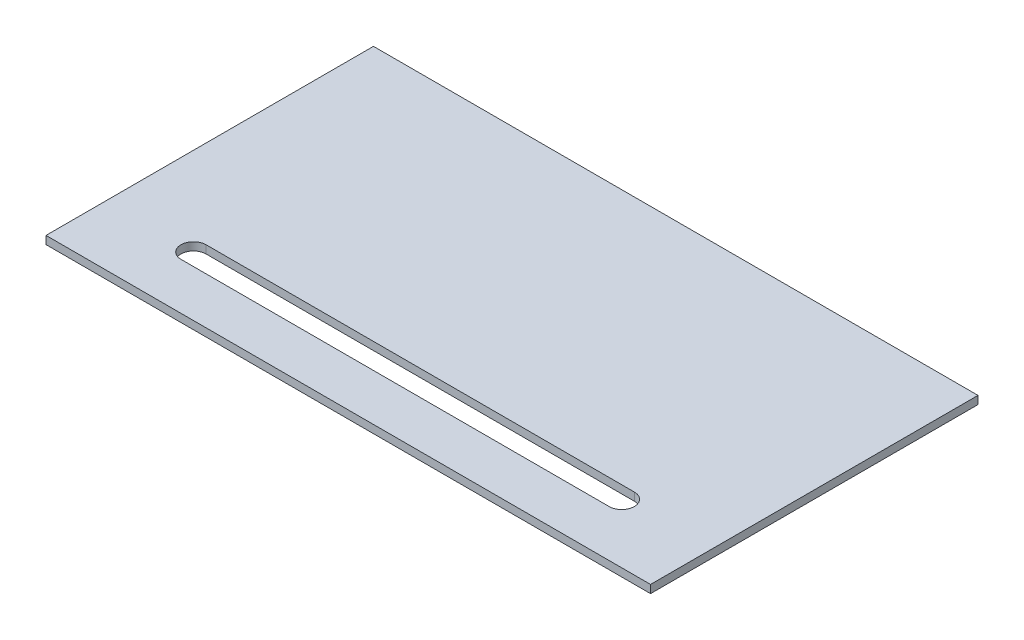
SolidWorks part; units mm, degrees
ref_plane "Front Plane" through (0, 0, 0) normal (0, 0, 1) x (1, 0, 0)
ref_plane "Top Plane" through (0, 0, 0) normal (0, 1, 0) x (1, 0, 0)
ref_plane "Right Plane" through (0, 0, 0) normal (1, 0, 0) x (0, 0, -1)
sketch "Sketch1" plane through (0, 0, 0) normal (0, 1, 0) x (1, 0, 0)
  line L0 (0, 65) -> (0, -65) construction
  line L1 (-120, 65) -> (120, 65)
  line L2 (-120, 65) -> (-120, -65)
  line L3 (-120, -65) -> (120, -65)
  line L4 (120, 65) -> (120, -65)
  line L5 (-111.5875, 55) -> (-111.5875, 45) construction
  line L6 (-113.175, 55) -> (-110, 55) construction
  line L7 (-113.175, 55) -> (-113.175, 45) construction
  line L8 (-113.175, 45) -> (-110, 45) construction
  line L9 (-110, 55) -> (-110, 45) construction
  line L10 (-110, 58.175) -> (-100, 58.175) construction
  line L11 (-110, 58.175) -> (-110, 55) construction
  line L12 (-110, 55) -> (-100, 55) construction
  line L13 (-100, 58.175) -> (-100, 55) construction
  line L14 (-110, 56.5875) -> (-100, 56.5875) construction
  line L15 (100, 56.5875) -> (110, 56.5875) construction
  line L16 (-113.175, 52) -> (-110, 52)
  line L17 (-113.175, 52) -> (-113.175, 48)
  line L18 (-113.175, 48) -> (-110, 48)
  line L19 (-110, 52) -> (-110, 48)
  line L20 (-113.175, 52) -> (-110, 48) construction
  line L21 (-113.175, 48) -> (-110, 52) construction
  line L22 (-107, 55) -> (-103, 55)
  line L23 (-107, 55) -> (-107, 58.175)
  line L24 (-107, 58.175) -> (-103, 58.175)
  line L25 (-103, 55) -> (-103, 58.175)
  line L26 (-107, 55) -> (-103, 58.175) construction
  line L27 (-107, 58.175) -> (-103, 55) construction
  line L28 (110, 55) -> (113.175, 55) construction
  line L29 (110, 55) -> (110, 45) construction
  line L30 (110, 45) -> (113.175, 45) construction
  line L31 (113.175, 55) -> (113.175, 45) construction
  line L32 (100, 58.175) -> (110, 58.175) construction
  line L33 (100, 58.175) -> (100, 55) construction
  line L34 (100, 55) -> (110, 55) construction
  line L35 (110, 58.175) -> (110, 55) construction
  line L36 (111.5875, 55) -> (111.5875, 45) construction
  line L37 (-111.5875, -45) -> (-111.5875, -55) construction
  line L38 (103, 55) -> (107, 55)
  line L39 (103, 55) -> (103, 58.175)
  line L40 (103, 58.175) -> (107, 58.175)
  line L41 (107, 55) -> (107, 58.175)
  line L42 (103, 55) -> (107, 58.175) construction
  line L43 (103, 58.175) -> (107, 55) construction
  line L44 (110, 52) -> (113.175, 52)
  line L45 (110, 52) -> (110, 48)
  line L46 (110, 48) -> (113.175, 48)
  line L47 (113.175, 52) -> (113.175, 48)
  line L48 (110, 52) -> (113.175, 48) construction
  line L49 (110, 48) -> (113.175, 52) construction
  line L50 (-113.175, -45) -> (-110, -45) construction
  line L51 (-113.175, -45) -> (-113.175, -55) construction
  line L52 (-113.175, -55) -> (-110, -55) construction
  line L53 (-110, -45) -> (-110, -55) construction
  line L54 (111.5875, -45) -> (111.5875, -55) construction
  line L55 (-113.175, -52) -> (-110, -52)
  line L56 (-113.175, -52) -> (-113.175, -48)
  line L57 (-113.175, -48) -> (-110, -48)
  line L58 (-110, -52) -> (-110, -48)
  line L59 (-113.175, -52) -> (-110, -48) construction
  line L60 (-113.175, -48) -> (-110, -52) construction
  line L61 (113.175, -55) -> (110, -55) construction
  line L62 (113.175, -55) -> (113.175, -45) construction
  line L63 (113.175, -45) -> (110, -45) construction
  line L64 (110, -55) -> (110, -45) construction
  line L65 (-70, -58.175) -> (-50, -58.175)
  line L66 (110, -52) -> (113.175, -52)
  line L67 (110, -52) -> (110, -48)
  line L68 (110, -48) -> (113.175, -48)
  line L69 (113.175, -52) -> (113.175, -48)
  line L70 (110, -52) -> (113.175, -48) construction
  line L71 (110, -48) -> (113.175, -52) construction
  line L72 (-110, -55) -> (-90, -55)
  line L73 (-110, -55) -> (-110, -58.175)
  line L74 (-110, -58.175) -> (-90, -58.175)
  line L75 (-90, -55) -> (-90, -58.175)
  line L76 (-70, -55) -> (-70, -58.175)
  line L77 (-70, -55) -> (-50, -55)
  line L78 (-50, -55) -> (-50, -58.175)
  line L79 (-30, -58.175) -> (-10, -58.175)
  line L80 (-30, -55) -> (-30, -58.175)
  line L81 (-30, -55) -> (-10, -55)
  line L82 (-10, -55) -> (-10, -58.175)
  line L83 (10, -58.175) -> (30, -58.175)
  line L84 (10, -55) -> (10, -58.175)
  line L85 (10, -55) -> (30, -55)
  line L86 (30, -55) -> (30, -58.175)
  line L87 (50, -58.175) -> (70, -58.175)
  line L88 (50, -55) -> (50, -58.175)
  line L89 (50, -55) -> (70, -55)
  line L90 (70, -55) -> (70, -58.175)
  line L91 (90, -58.175) -> (110, -58.175)
  line L92 (90, -55) -> (90, -58.175)
  line L93 (90, -55) -> (110, -55)
  line L94 (110, -55) -> (110, -58.175)
  line L191 (-68.5, -21.825) -> (-64.5, -21.825)
  line L192 (-68.5, -21.825) -> (-68.5, -25)
  line L193 (-68.5, -25) -> (-64.5, -25)
  line L194 (-64.5, -21.825) -> (-64.5, -25)
  line L195 (-57, -21.825) -> (-53, -21.825)
  line L196 (-57, -21.825) -> (-57, -25)
  line L197 (-57, -25) -> (-53, -25)
  line L198 (-53, -21.825) -> (-53, -25)
  line L199 (-45.5, -21.825) -> (-41.5, -21.825)
  line L200 (-45.5, -21.825) -> (-45.5, -25)
  line L201 (-45.5, -25) -> (-41.5, -25)
  line L202 (-41.5, -21.825) -> (-41.5, -25)
  line L216 (41.5, -25) -> (45.5, -25)
  line L217 (41.5, -25) -> (41.5, -21.825)
  line L218 (41.5, -21.825) -> (45.5, -21.825)
  line L219 (45.5, -25) -> (45.5, -21.825)
  line L220 (53, -25) -> (57, -25)
  line L221 (53, -25) -> (53, -21.825)
  line L222 (53, -21.825) -> (57, -21.825)
  line L223 (57, -25) -> (57, -21.825)
  line L224 (64.5, -25) -> (68.5, -25)
  line L225 (64.5, -25) -> (64.5, -21.825)
  line L226 (64.5, -21.825) -> (68.5, -21.825)
  line L227 (68.5, -25) -> (68.5, -21.825)
  line L240 (-13.5, -21.825) -> (-9.5, -21.825)
  line L241 (-13.5, -21.825) -> (-13.5, -25)
  line L242 (-13.5, -25) -> (-9.5, -25)
  line L243 (-9.5, -21.825) -> (-9.5, -25)
  line L244 (-2, -25) -> (2, -25)
  line L245 (-2, -25) -> (-2, -21.825)
  line L246 (-2, -21.825) -> (2, -21.825)
  line L247 (2, -25) -> (2, -21.825)
  line L248 (9.5, -25) -> (13.5, -25)
  line L249 (9.5, -25) -> (9.5, -21.825)
  line L250 (9.5, -21.825) -> (13.5, -21.825)
  line L251 (13.5, -25) -> (13.5, -21.825)
  line L252 (-57, -25) -> (-33.85, -25)
  line L253 (-85, -36.4381) -> (-85, -46.4381) construction
  line L254 (-68.5, -21.825) -> (-64.5, -21.825)
  line L255 (-68.5, -21.825) -> (-68.5, -25)
  line L256 (-68.5, -25) -> (-64.5, -25)
  line L257 (-64.5, -21.825) -> (-64.5, -25)
  line L261 (-68.5, -25) -> (-64.5, -25)
  line L263 (-76.15, 17.3) -> (-33.85, -25) construction
  line L264 (-55, -3.85) -> (-33.85, 17.3) construction
  line L266 (-85, -36.4381) -> (85, -36.4381)
  line L269 (-57, -21.825) -> (-57, -25)
  line L270 (-68.5, -21.825) -> (-68.5, -25)
  line L271 (-68.5, -25) -> (-64.5, -25)
  line L272 (-64.5, -21.825) -> (-64.5, -25)
  line L273 (-41.5, -21.825) -> (-41.5, -25)
  line L274 (-41.5, -25) -> (-45.5, -25)
  line L275 (-45.5, -21.825) -> (-45.5, -25)
  line L276 (-57, -25) -> (-53, -25)
  line L277 (-53, -21.825) -> (-53, -25)
  line L278 (-85, -46.4381) -> (85, -46.4381)
  line L280 (-57, -21.825) -> (-53, -21.825)
  line L281 (-45.5, -21.825) -> (-41.5, -21.825)
  line L282 (-68.5, -21.825) -> (-64.5, -21.825)
  line L291 (-55, 17.3) -> (-55, -21.825) construction
  line L293 (85, -36.4381) -> (85, -46.4381) construction
  arc A0 (-85, -36.4381) -> (-85, -46.4381) centre (-85, -41.4381) ccw
  arc A1 (85, -36.4381) -> (85, -46.4381) centre (85, -41.4381) cw
  point P19 (-111.5875, 50)
  point P24 (-105, 56.5875)
  point P41 (105, 56.5875)
  point P46 (111.5875, 50)
  point P57 (-111.5875, -50)
  point P68 (111.5875, -50)
  point P77 (-55, -25)
  point P121 (55, -25)
  point P134 (0, -25)
  point P135 (-55, -25)
  point P166 (-55, -23.4125)
  dimension "D1" = 240
  dimension "D2" = 130
  dimension "D3" = 65
  dimension "D4" = 120
  dimension "D5" = 6.825
  dimension "D6" = 6.825
  dimension "D7" = 10
  dimension "D8" = 10
  dimension "D9" = 3.175
  dimension "D10" = 10
  dimension "D11" = 4
  dimension "D12" = 4
  dimension "D13" = 6.825
  dimension "D14" = 6.825
  dimension "D15" = 10
  dimension "D16" = 10
  dimension "D17" = 10
  dimension "D18" = 3.175
  dimension "D19" = 4
  dimension "D20" = 4
  dimension "D21" = 6.825
  dimension "D22" = 10
  dimension "D23" = 10
  dimension "D24" = 3.175
  dimension "D25" = 4
  dimension "D26" = 6.825
  dimension "D27" = 3.175
  dimension "D28" = 10
  dimension "D29" = 10
  dimension "D30" = 4
  dimension "D31" = 20
  dimension "D32" = 3.175
  dimension "D39" = 3.175
  dimension "D34" = 7.5
  dimension "D35" = 7.5
  dimension "D36" = 55
  dimension "D38" = 4
  dimension "D40" = 3.175
  dimension "D41" = 7.5
  dimension "D42" = 7.5
  dimension "D43" = 55
  dimension "D44" = 30
  dimension "D45" = 30
  dimension "D46" = 4
  dimension "D47" = 3.175
  dimension "D48" = 7.5
  dimension "D49" = 7.5
  dimension "D50" = 30
  dimension "D51" = 42.3
  dimension "D52" = 42.3
  dimension "D57" = 4
  dimension "D58" = 3.175
  dimension "D59" = 7.5
  dimension "D60" = 7.5
  dimension "D37" = 10
  dimension "D33" = 6
extrude "Boss-Extrude4" add sketch "Sketch1" along normal blind 3.175 contours L4 L1 L2 L3 L251 L248 L249 L250 L247 L244 L245 L246 L227 L224 L225 L226 L223 L220 L221 L222 L219 L216 L217 L218 L69 L66 L67 L68 L58 L55 L56 L57 L41 L38 L39 L40 L25 L22 L23 L24 L16 | L75 L72 L73 L74 | L55 L58 L57 L56 | L78 L77 L76 L65 | L194 L191 L192 L193 | L198 L195 L196 L197 | L202 L199 L200 L201 | L94 L93 L92 L91 | L82 L81 L80 L79 | L86 L85 L84 L83 | L248 L251 L250 L249 | L244 L247 L246 L245 | L243 L240 L241 L242 | L90 L89 L88 L87 | L224 L227 L226 L225 | L220 L223 L222 L221 | L216 L219 L218 L217 | L19 L16 L17 L18 | L22 L25 L24 L23 | L38 L41 L40 L39 | L47 L44 L45 L46 | L66 L69 L68 L67 region at (0, 0, -3.3448) region at (-111.5875, 0, -50) region at (-105, 0, -56.5875) region at (105, 0, -56.5875) region at (111.5875, 0, -50) region at (-111.5875, 0, 50) region at (-60, 0, 56.5875) region at (111.5875, 0, 50) region at (-100, 0, 56.5875) region at (-20, 0, 56.5875) region at (20, 0, 56.5875) region at (60, 0, 56.5875) region at (100, 0, 56.5875) region at (-66.5, 0, 23.4125) region at (-43.5, 0, 23.4125) region at (-55, 0, 23.4125) region at (43.5, 0, 23.4125) region at (55, 0, 23.4125) region at (66.5, 0, 23.4125) region at (-11.5, 0, 23.4125) region at (0, 0, 23.4125) region at (11.5, 0, 23.4125)
equation "\"stepper width\"=4.23"
equation "\"stepper hole disctance\"= 3.1"
equation "\"stepper hole diameter\"=0.34"
equation "\"stepper shaft hole\"=2.4"
equation "\"tooth width\"=0.4"
equation "\"tooth thickness\"=0.3175"
equation "\"tooth to side\"=0.75"
equation "\"motor chamber height\"= 6"
equation "\"enclosure length\"= 22"
equation "\"platform diameter\"= 9cm"
equation "\"teeth width\"=0.3175"
equation "\"teeth lenght\"=2"
equation "\"tower width\"=7.7"
equation "\"D1@Sketch1\"=\"enclosure length\"+2"
equation "\"D2@Sketch1\"=\"enclosure length\"/2+2"
equation "\"D3@Sketch1\"=\"enclosure length\"/4+1"
equation "\"D4@Sketch1\"=\"enclosure length\"/2+1"
equation "\"D5@Sketch1\"=1 - \"tooth thickness\""
equation "\"D6@Sketch1\"=1 - \"tooth thickness\""
equation "\"D9@Sketch1\"=\"teeth width\""
equation "\"support width\"=1"
equation "\"D10@Sketch1\"=\"support width\""
equation "\"D11@Sketch1\"=\"tooth width\""
equation "\"D12@Sketch1\"=\"tooth width\""
equation "\"D13@Sketch1\"=1 - \"tooth thickness\""
equation "\"D14@Sketch1\"=1 - \"tooth thickness\""
equation "\"D17@Sketch1\"=\"support width\""
equation "\"D18@Sketch1\"=\"tooth thickness\""
equation "\"D19@Sketch1\"=\"tooth width\""
equation "\"D20@Sketch1\"=\"tooth width\""
equation "\"D21@Sketch1\"=1 - \"tooth thickness\""
equation "\"D23@Sketch1\"=\"support width\""
equation "\"D24@Sketch1\"=\"tooth thickness\""
equation "\"D25@Sketch1\"=\"tooth width\""
equation "\"D26@Sketch1\"=1 - \"tooth thickness\""
equation "\"D27@Sketch1\"=\"tooth thickness\""
equation "\"D28@Sketch1\"=\"support width\""
equation "\"D30@Sketch1\"=\"tooth width\""
equation "\"D31@Sketch1\"=\"teeth lenght\""
equation "\"D32@Sketch1\"=\"tooth thickness\""
equation "\"trial hole spacing\"= 0.75"
equation "\"mounting distance\"= 4"
equation "\"D39@Sketch1\"=\"tooth thickness\""
equation "\"D34@Sketch1\"=\"tooth to side\""
equation "\"half belt distance\"=5.5"
equation "\"D36@Sketch1\"=\"half belt distance\""
equation "\"D38@Sketch1\"=\"tooth width\""
equation "\"D40@Sketch1\"=\"tooth thickness\""
equation "\"D41@Sketch1\"=\"tooth to side\""
equation "\"D42@Sketch1\"=\"tooth to side\""
equation "\"D43@Sketch1\"=\"half belt distance\""
equation "\"holder distance to wall\"=3"
equation "\"D44@Sketch1\"=\"holder distance to wall\""
equation "\"D45@Sketch1\"=\"holder distance to wall\""
equation "\"D46@Sketch1\"=\"tooth width\""
equation "\"D47@Sketch1\"=\"tooth thickness\""
equation "\"D48@Sketch1\"=\"tooth to side\""
equation "\"D49@Sketch1\"=\"tooth to side\""
equation "\"D50@Sketch1\"=\"holder distance to wall\""
equation "\"pusher hole width\"=1"
equation "\"D37@Sketch1\"=\"pusher hole width\""
